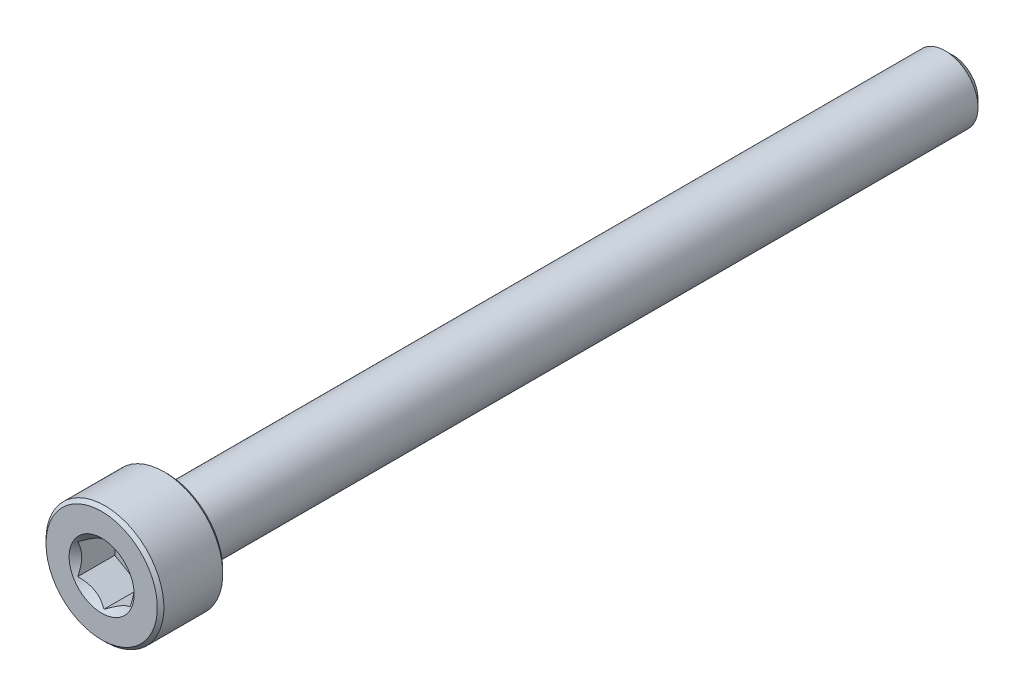
SolidWorks part; units mm, degrees
ref_plane "Front Plane" through (0, 0, 0) normal (0, 0, 1) x (1, 0, 0)
ref_plane "Top Plane" through (0, 0, 0) normal (0, 1, 0) x (1, 0, 0)
ref_plane "Right Plane" through (0, 0, 0) normal (1, 0, 0) x (0, 0, -1)
sketch "Sketch1" plane through (0, 0, 0) normal (1, 0, 0) x (0, 0, -1)
  line L0 (-16.25, 0) -> (16.25, 0) construction
  line L1 (16.25, 0) -> (16.25, 0.9577) construction
  line L2 (16.25, 0.9577) -> (15.9577, 1.25) construction
  line L3 (15.9577, 1.25) -> (15.9125, 1.25) construction
  line L4 (15.9125, 1.25) -> (-13.75, 1.25) construction
  line L5 (-13.75, 1.25) -> (-13.75, 2.25) construction
  line L6 (-13.75, 2.25) -> (-16.25, 2.25) construction
  line L7 (-16.25, 2.25) -> (-16.25, 0) construction
  line L8 (16.25, 0.9577) -> (16.25, 1.25) construction
  line L9 (16.2219, 1.2987) -> (16.4469, 0.909) construction
  line L10 (16.4469, 0.909) -> (16.6719, 1.2987) construction
  line L11 (16.6719, 1.2987) -> (16.2219, 1.2987) construction
  line L12 (16.4469, 1.2987) -> (16.4469, 1.25) construction
  line L13 (16.4469, 0.909) -> (16.4469, 0.9577) construction
  line L14 (16.4188, 0.9577) -> (16.475, 0.9577) construction
  line L15 (16.25, 1.25) -> (16.6437, 1.25) construction
  line L16 (16.2359, 1.2744) -> (16.6578, 1.2744) construction
  line L17 (16.25, 0) -> (16.25, -1.25) construction
  line L18 (-13.875, 2.25) -> (-13.75, 2.125) construction
  line L19 (-16.125, 2.25) -> (-16.25, 2.125) construction
  line L20 (-13.75, 1.25) -> (-13.75, 0) construction
  line L21 (-13.75, 0.625) -> (-3.75, 0.625) construction
  line L22 (-3.75, 0.625) -> (6.25, 0.625) construction
  line L23 (6.25, 0.625) -> (16.25, 0.625) construction
  line L24 (-3.75, 0.625) -> (-3.75, 1.25) construction
  line L25 (-3.75, 1.25) -> (-3.75, 2.25) construction
  line L26 (6.25, 0.625) -> (6.25, 2.25) construction
  point P0 (-16.25, 1)
  point P3 (15.125, 1.25)
  point P4 (0, 0)
  point P18 (6.25, 1.25)
  point P22 (16.4469, 0.9577)
  point P24 (15.9125, 1.25)
  point P25 (16.4469, 1.25)
  point P28 (16.4469, 1.2744)
  point P29 (15.125, -1.25)
  point P30 (-3.75, 1.25)
  point P31 (-15, 2.25)
  point P37 (-14.1875, 2.25)
  point P38 (-16.0625, 2.25)
  point P45 (-3.75, 0.625)
  point P46 (6.25, 0.625)
  dimension "D2" = 0.0563
  dimension "D7" = 0.125
  dimension "D8" = 0.125
  dimension "D9" = 0.125
  dimension "D10" = 0.0625
  dimension "D11" = 0.3125
  dimension "Drive Size" = 2
  dimension "Head Diameter" = 4.5
  dimension "Head Height" = 2.5
  dimension "Thread Pitch" = 0.45
  dimension "Thread Dia" = 2.5
  dimension "Length" = 30
  dimension "D12" = 0.3375
  dimension "D4" = 1.125
  dimension "D3" = 45
sketch "Sketch2" plane through (0, 0, 0) normal (1, 0, 0) x (0, 0, -1)
  line L0 (-16.25, 0) -> (-16.25, 2.125)
  line L1 (-16.125, 2.25) -> (-13.875, 2.25)
  line L2 (-13.75, 2.125) -> (-13.75, 1.375)
  line L4 (15.9577, 1.25) -> (16.25, 0.9577)
  line L5 (16.25, 0.9577) -> (16.25, 0)
  line L6 (-13.75, 2.25) -> (-16.25, 2.25) construction
  line L7 (16.25, 0) -> (-16.25, 0)
  line L8 (-16.125, 2.25) -> (-16.25, 2.125) construction
  line L10 (-16.125, 2.25) -> (-16.25, 2.125)
  line L14 (-13.875, 2.25) -> (-13.75, 2.125) construction
  line L16 (-13.875, 2.25) -> (-13.75, 2.125)
  line L17 (-13.75, 1.25) -> (-13.75, 2.25) construction
  line L19 (-13.625, 1.25) -> (15.9577, 1.25)
  line L20 (15.9125, 1.25) -> (-13.75, 1.25) construction
  arc A1 (-13.75, 1.375) -> (-13.625, 1.25) centre (-13.625, 1.375) ccw
  dimension "D3" = 0.125
revolve "Revolve1" add sketch "Sketch2" angle 360 about L7
sketch "Sketch3" plane through (0, 0, 16.25) normal (0, 0, 1) x (1, 0, 0)
  line L1 (1, -0.5774) -> (1, 0.5774)
  line L2 (1, 0.5774) -> (0, 1.1547)
  line L3 (0, 1.1547) -> (-1, 0.5774)
  line L4 (-1, 0.5774) -> (-1, -0.5774)
  line L5 (-1, -0.5774) -> (0, -1.1547)
  line L6 (0, -1.1547) -> (1, -0.5774)
  circle A0 centre (0, 0) radius 1 construction
  circle A1 centre (0, 0) radius 2.25 construction
  circle A2 centre (0, 0) radius 2.25 construction
  circle A3 centre (0, 0) radius 1.1547 construction
  point P13 (0, 0)
  dimension "D1" = 2.3094
extrude "Cut-Extrude1" cut sketch "Sketch3" against normal offset from surface (1.5 mm away) 1 up to face at (-2.125, 0, 13.75)
sketch "Sketch4" plane through (0, 0, 16.25) normal (0, 0, 1) x (1, 0, 0)
  circle A0 centre (0, 0) radius 1.2413
  dimension "D1" = 2.4826
extrude "Cut-Extrude2" cut sketch "Sketch4" against normal up to vertex (1.25 mm away) draft 45 up to point (0, 2.25, 15)
sketch "Sketch11" plane through (0, 0, 0) normal (1, 0, 0) x (0, 0, -1)
  line L0 (-16.25, 0) -> (16.25, 0) construction
  line L1 (-16.25, 0) -> (16.25, 0) construction
  line L2 (-8.125, 0) -> (-8.125, 1.25) construction
  line L3 (15.9125, 1.25) -> (-13.75, 1.25) construction
  line L4 (10.625, 0) -> (10.625, 1.25) construction
  line L6 (16.25, 0.9577) -> (16.25, 1.25) construction
  point P2 (-8.125, 0)
  point P3 (10.625, 0)
  dimension "D1" = 5.625
  dimension "D2" = 5.625
sketch "Sketch6" [suppressed] plane through (0, 0, -16.25) normal (0, 0, -1) x (-1, 0, 0)
  circle A0 centre (0, 0) radius 1.25
curve "Helix/Spiral1" [suppressed] pitch 0.45 height 30.45 turns 67.6667
sketch "Sketch10" [suppressed] plane through (0, 0, 0) normal (1, 0, 0) x (0, 0, -1)
  line L0 (-13.625, -2.25) -> (-13.625, 2.25)
  line L5 (-16.25, 0) -> (16.25, 0) construction
  line L6 (-13.625, 1.25) -> (-13.625, -1.25) construction
  point P3 (-13.625, 0)
split "Split1" [suppressed] bodies to split 106
sketch "Sketch7" [suppressed] plane through (0, 0, 0) normal (1, 0, 0) x (0, 0, -1)
  line L0 (16.2359, 1.2744) -> (16.6578, 1.2744)
  line L1 (16.6578, 1.2744) -> (16.475, 0.9577)
  line L2 (16.475, 0.9577) -> (16.4188, 0.9577)
  line L3 (16.4188, 0.9577) -> (16.2359, 1.2744)
sweep "Cut-Sweep1" [suppressed] cut profiles "Sketch7" path "Helix/Spiral1"
sketch "Sketch8" [suppressed] plane through (0, 0, 0) normal (1, 0, 0) x (0, 0, -1)
  line L0 (-13.75, 0) -> (-13.75, 1.25)
  line L1 (-13.625, -1.25) -> (-13.625, 1.25) construction
  line L2 (-13.75, 1.25) -> (-13.625, 1.25)
  line L4 (-13.625, 1.25) -> (-12.9033, 0)
  line L5 (-12.9033, 0) -> (-13.75, 0)
  line L6 (15.9125, 1.25) -> (-13.75, 1.25) construction
  line L7 (-16.25, 0) -> (16.25, 0) construction
  dimension "D1" = 60
revolve "Revolve2" [suppressed] add sketch "Sketch8" angle 360 about L5
equation "\"D2@Sketch1\" = \"Thread Pitch@Sketch1\" / 8"
equation "\"D4@Helix/Spiral1\" = \"Thread Pitch@Sketch1\""
equation "\"D7@Sketch1\" = \"Head Height@Sketch1\" * .05"
equation "\"D8@Sketch1\"=\"D7@Sketch1\""
equation "\"D9@Sketch1\"=\"D7@Sketch1\""
equation "\"D10@Sketch1\"=\"D7@Sketch1\"/2"
equation "\"D11@Sketch1\"=\"D10@Sketch1\"*5"
equation "\"D4@Sketch1\"=\"Thread Pitch@Sketch1\"*2.5"
equation "\"D12@Sketch1\"=\"Thread Pitch@Sketch1\"*.75"
equation "\"D3@Helix/Spiral1\"=\"Length@Sketch1\"+\"Thread Pitch@Sketch1\""
equation "\"D3@Sketch2\"=\"Thread Dia@Sketch1\"*0.05"
equation "\"D1@Sketch11\"=\"Length@Sketch1\"*0.1875"
equation "\"D2@Sketch11\"=\"D1@Sketch11\""
equation "\"D1@Sketch4\"=\"D1@Sketch3\"*1.075"
